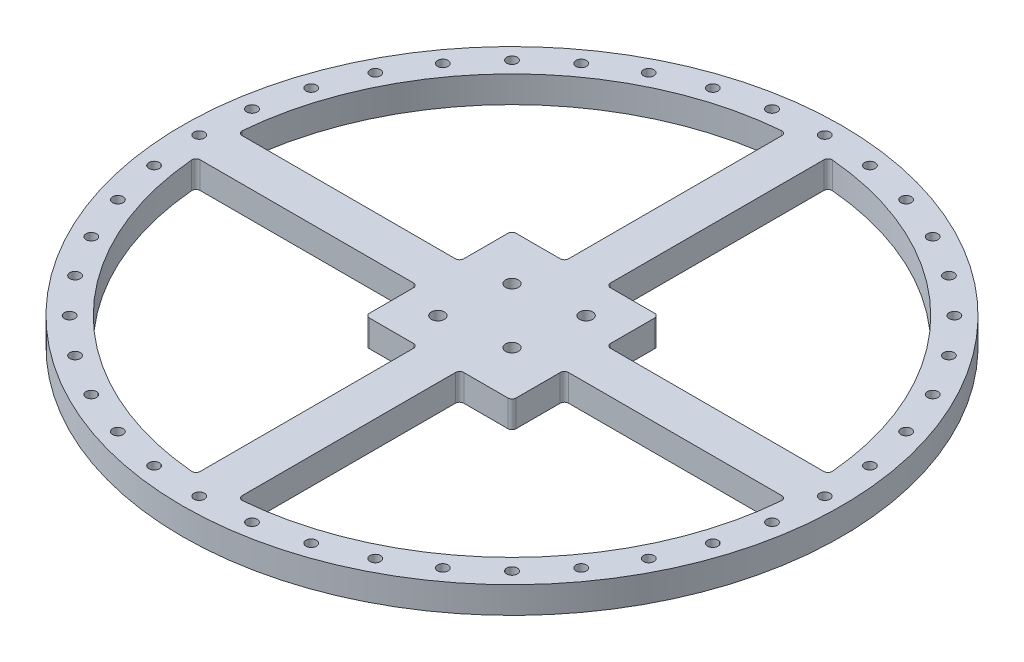
SolidWorks part; units mm, degrees
ref_plane "Front Plane" through (0, 0, 0) normal (0, 0, 1) x (1, 0, 0)
ref_plane "Top Plane" through (0, 0, 0) normal (0, 1, 0) x (1, 0, 0)
ref_plane "Right Plane" through (0, 0, 0) normal (1, 0, 0) x (0, 0, -1)
sketch "Sketch1" plane through (0, 0, 0) normal (0, 1, 0) x (1, 0, 0)
  line L1 (-14.236, 18.3559) -> (20.764, 18.3559)
  line L2 (-14.236, 18.3559) -> (-14.236, -16.6441)
  line L3 (-14.236, -16.6441) -> (20.764, -16.6441)
  line L4 (20.764, 18.3559) -> (20.764, -16.6441)
  dimension "D1" = 35
extrude "Boss-Extrude1" add sketch "Sketch1" along normal blind 6.35
sketch "Sketch2" plane through (0, 6.35, 0) normal (0, 1, 0) x (1, 0, 0)
  line L0 (-14.236, 18.3559) -> (20.764, -16.6441) construction
  line L1 (-14.236, -16.6441) -> (20.764, 18.3559) construction
  circle A0 centre (-3.3474, 7.4673) radius 1.55
  circle A1 centre (12.1028, 9.6947) radius 1.55
  circle A2 centre (9.8755, -5.7556) radius 1.55
  circle A3 centre (-5.5748, -7.983) radius 1.55
  dimension "D1" = 3.1
  dimension "D2" = 18.7
  dimension "D3" = 25
extrude "Cut-Extrude1" cut sketch "Sketch2" against normal through all
sketch "Sketch3" plane through (20.764, 0, 0) normal (1, 0, 0) x (0, 0, -1)
  line L0 (-16.6441, 6.35) -> (18.3559, 6.35) construction
  line L1 (-4.1441, 6.35) -> (5.8559, 6.35)
  line L2 (-4.1441, 6.35) -> (-4.1441, 0)
  line L3 (-4.1441, 0) -> (5.8559, 0)
  line L4 (5.8559, 6.35) -> (5.8559, 0)
  line L5 (-16.6441, 0) -> (18.3559, 0) construction
  line L6 (0.8559, 6.35) -> (0.8559, 0) construction
  dimension "D1" = 10
extrude "Boss-Extrude2" add sketch "Sketch3" along normal blind 60.96
sketch "Sketch4" plane through (0, 0, 16.6441) normal (0, 0, 1) x (1, 0, 0)
  line L0 (3.264, 6.35) -> (3.264, 0) construction
  line L1 (-14.236, 6.35) -> (20.764, 6.35) construction
  line L2 (-14.236, 0) -> (20.764, 0) construction
  line L4 (-1.736, 6.35) -> (8.264, 6.35)
  line L5 (-1.736, 6.35) -> (-1.736, 0)
  line L6 (-1.736, 0) -> (8.264, 0)
  line L7 (8.264, 6.35) -> (8.264, 0)
  dimension "D1" = 10
extrude "Boss-Extrude3" add sketch "Sketch4" along normal blind 60.96
sketch "Sketch5" plane through (-14.236, 0, 0) normal (-1, 0, 0) x (0, 0, 1)
  line L0 (-0.8559, 6.35) -> (-0.8559, 0) construction
  line L4 (-18.3559, 6.35) -> (16.6441, 6.35) construction
  line L5 (-18.3559, 0) -> (16.6441, 0) construction
  line L7 (-5.8559, 6.35) -> (4.1441, 6.35)
  line L8 (-5.8559, 6.35) -> (-5.8559, 0)
  line L9 (-5.8559, 0) -> (4.1441, 0)
  line L10 (4.1441, 6.35) -> (4.1441, 0)
  dimension "D1" = 10
extrude "Boss-Extrude4" add sketch "Sketch5" along normal blind 60.96
sketch "Sketch6" plane through (0, 0, -18.3559) normal (0, 0, -1) x (-1, 0, 0)
  line L0 (-3.264, 6.35) -> (-3.264, 0) construction
  line L1 (-20.764, 6.35) -> (14.236, 6.35) construction
  line L2 (-20.764, 0) -> (14.236, 0) construction
  line L4 (-8.264, 6.35) -> (1.736, 6.35)
  line L5 (-8.264, 6.35) -> (-8.264, 0)
  line L6 (-8.264, 0) -> (1.736, 0)
  line L7 (1.736, 6.35) -> (1.736, 0)
  dimension "D1" = 10
extrude "Boss-Extrude5" add sketch "Sketch6" along normal blind 60.96
sketch "Sketch7" plane through (0, 0, 4.1441) normal (0, 0, 1) x (1, 0, 0)
  line L0 (81.724, 0) -> (20.764, 0) construction
  line L1 (81.724, 6.35) -> (73.724, 6.35)
  line L2 (81.724, 6.35) -> (81.724, 0)
  line L3 (81.724, 0) -> (73.724, 0)
  line L4 (73.724, 6.35) -> (73.724, 0)
  dimension "D1" = 8
sketch "Sketch8" plane through (0, 6.35, 0) normal (0, 1, 0) x (1, 0, 0)
  line L0 (20.764, 18.3559) -> (-14.236, -16.6441) construction
  line L1 (-14.236, 18.3559) -> (20.764, -16.6441) construction
  circle A0 centre (3.264, 0.8559) radius 78.6192
  point P8 (3.264, 0.8559)
sweep "Sweep1" add profiles "Sketch7" path "Sketch8"
fillet "Fillet1" radius 1 12 edges at (20.764, 3.175, -18.3559) (20.764, 3.175, 16.6441) (-14.236, 3.175, 16.6441) (-14.236, 3.175, -18.3559)
sketch "Sketch9" plane through (0, 6.35, 0) normal (0, 1, 0) x (1, 0, 0)
  circle A0 centre (3.264, 0.8559) radius 74.6192 construction
  circle A1 centre (3.264, 0.8559) radius 78.6192 construction
  circle A3 centre (3.264, -73.7633) radius 1.25
  dimension "D1" = 4
  dimension "D2" = 2.5
extrude "Cut-Extrude2" cut sketch "Sketch9" against normal through all
pattern_circular "CirPattern1" count 40 over 360 about axis through (3.264, 6.35, -0.8559) along (0, -1, 0) of "Cut-Extrude2"
fillet "Fillet2" radius 1 8 edges at (-1.736, 3.175, 69.6041) (8.264, 3.175, 69.6041) (73.724, 3.175, -5.8559) (73.724, 3.175, 4.1441) (-67.196, 3.175, -5.8559) (-67.196, 3.175, 4.1441) (-1.736, 3.175, -71.3159) (8.264, 3.175, -71.3159)
